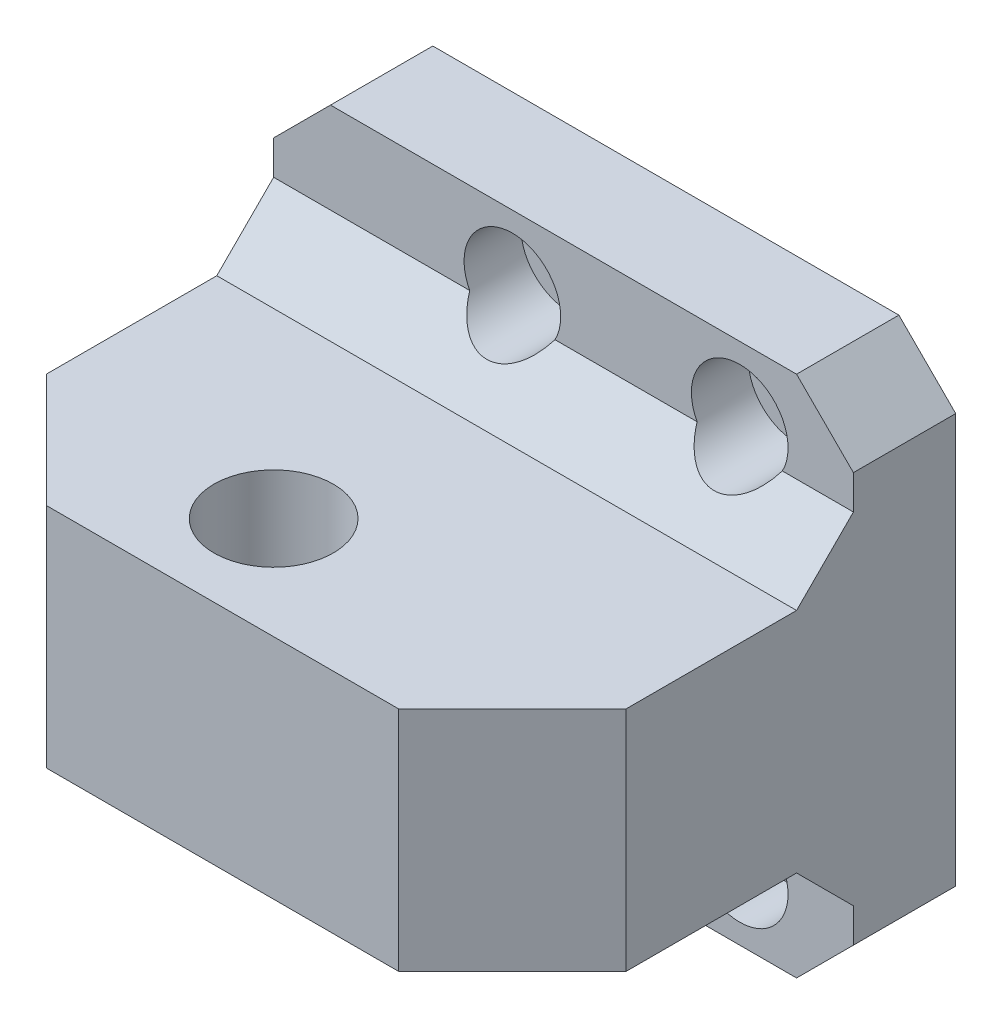
SolidWorks part; units mm, degrees
ref_plane "前基準面" through (0, 0, 0) normal (0, 0, 1) x (1, 0, 0)
ref_plane "上基準面" through (0, 0, 0) normal (0, 1, 0) x (1, 0, 0)
ref_plane "右基準面" through (0, 0, 0) normal (1, 0, 0) x (0, 0, -1)
sketch "草圖1" plane through (0, 0, 0) normal (0, 0, 1) x (1, 0, 0)
  line L0 (30, 23) -> (21, 23)
  line L1 (-21, 23) -> (21, 23)
  line L2 (-21, 23) -> (-21, -23)
  line L3 (-21, -23) -> (21, -23)
  line L4 (30, -23) -> (21, -23)
  line L9 (30, 23) -> (30, -23)
  circle A0 centre (0, 17) radius 2.75
  circle A1 centre (20, 17) radius 2.75
  circle A3 centre (20, -17) radius 2.75
  circle A5 centre (0, -17) radius 2.75
  circle A6 centre (0, 0) radius 2.75 [skipped]
  circle A7 centre (20, 0) radius 2.75 [skipped]
  point P4 (0, 23)
  point P6 (-21, 0)
  point P10 (30, 0)
  point P13 (0, 0)
  dimension "D3" = 5.5
  dimension "D4" = 6
  dimension "D7" = 6
  dimension "D1" = 42
  dimension "D2" = 46
  dimension "D5" = 2
  dimension "D10" = 10
  dimension "D6" = 3
extrude "填料-伸長1" add sketch "草圖1" along normal blind 9
sketch "草圖6" plane through (0, 0, 9) normal (0, 0, 1) x (1, 0, 0)
  circle A0 centre (0, 17) radius 4.25
  circle A1 centre (20, 17) radius 4.25
  circle A2 centre (20, 17) radius 2.75 construction
  circle A3 centre (20, -17) radius 4.25
  circle A4 centre (20, -17) radius 2.75 construction
  circle A5 centre (0, -17) radius 4.25
  circle A6 centre (20, 0) radius 4.25 [skipped]
  circle A7 centre (0, 0) radius 4.25 [skipped]
  point P3 (0, 0)
  point P4 (0, 0)
  dimension "D1" = 8.5
  dimension "D2" = 2
  dimension "D3" = 3
extrude "除料-伸長3" cut sketch "草圖6" against normal blind 5
chamfer "導角2" distance 5 angle 45 4 edges at (-21, 23, 4.5) (30, 23, 4.5) (-21, -23, 4.5) (30, -23, 4.5)
sketch "草圖8" plane through (0, 0, 9) normal (0, 0, 1) x (1, 0, 0)
  line L0 (-21, 18) -> (-21, -18) construction
  line L1 (-21, -10) -> (30, -10)
  line L2 (-21, -10) -> (-21, 10)
  line L3 (-21, 10) -> (30, 10)
  line L4 (30, -10) -> (30, 10)
  line L5 (30, -18) -> (30, 18) construction
  point P8 (30, 0)
  dimension "D1" = 20
extrude "填料-伸長2" add sketch "草圖8" along normal blind 30
sketch "草圖9" plane through (0, 10, 0) normal (0, 1, 0) x (1, 0, 0)
  line L1 (30, -9) -> (-21, -9) construction
  line L2 (-21, -39) -> (-21, -9) construction
  circle A0 centre (0, -30) radius 5.25
  dimension "D3" = 10.5
  dimension "D1" = 21
  dimension "D2" = 21
extrude "除料-伸長4" cut sketch "草圖9" against normal through all
chamfer "導角3" distance 10 angle 45 2 edges at (-21, 0, 39) (30, 0, 39)
chamfer "導角4" distance 5 angle 45 2 edges at (4.5, 10, 9) (4.5, -10, 9)
